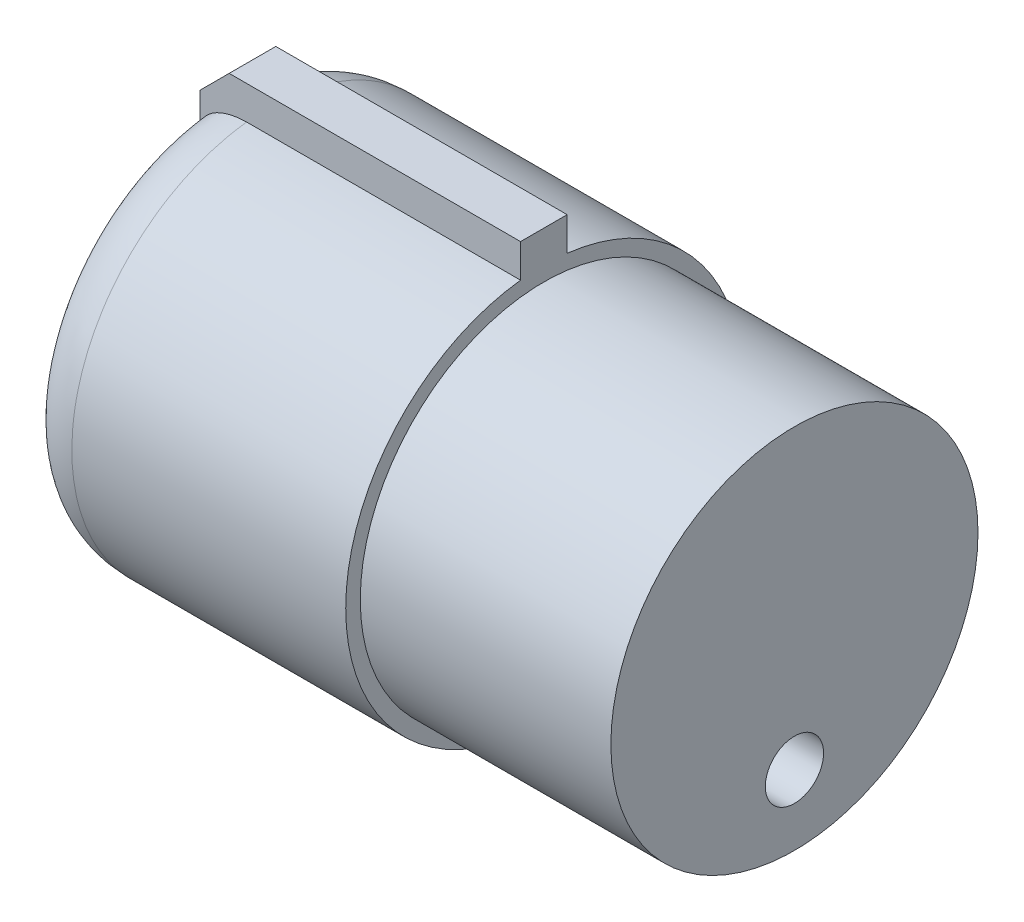
SolidWorks part; units mm, degrees
material "PET"
ref_plane "Front Plane" through (0, 0, 0) normal (0, 0, 1) x (1, 0, 0)
ref_plane "Top Plane" through (0, 0, 0) normal (0, 1, 0) x (1, 0, 0)
ref_plane "Right Plane" through (0, 0, 0) normal (1, 0, 0) x (0, 0, -1)
sketch "Sketch1" plane through (0, 0, 0) normal (0, 0, 1) x (1, 0, 0)
  line L0 (0, 0) -> (8.8, 0) construction
  line L1 (8.8, 0) -> (8.8, 2.5)
  line L2 (8.8, 2.5) -> (4.85, 2.5)
  line L3 (4.85, 2.5) -> (4.85, 2.75)
  line L4 (4.85, 2.75) -> (0, 2.75)
  line L5 (0, 2.75) -> (0, 3.4)
  line L6 (0, 3.4) -> (5.5, 3.4)
  line L7 (5.5, 3.4) -> (5.5, 3.15)
  line L8 (5.5, 3.15) -> (9.8, 3.15)
  line L9 (9.8, 3.15) -> (9.8, 0)
  line L10 (9.8, 0) -> (8.8, 0)
  point P12 (8.8, 0.3857)
  dimension "D1" = 8.8
  dimension "D2" = 1
  dimension "D3" = 3.4
  dimension "D4" = 5.5
  dimension "D5" = 3.15
  dimension "D6" = 0.65
  dimension "D7" = 0.65
  dimension "D8" = 0.65
revolve "Revolve1" add sketch "Sketch1" angle 360 about L0
sketch "Sketch2" plane through (0, 0, 0) normal (-1, 0, 0) x (0, 0, 1)
  line L0 (0, 2.95) -> (0, 0) construction
  line L1 (0.4, 2.95) -> (-0.4, 2.95)
  line L2 (0.4, 2.95) -> (0.4, 3.95)
  line L3 (0.4, 3.95) -> (-0.4, 3.95)
  line L4 (-0.4, 2.95) -> (-0.4, 3.95)
  line L5 (0.4, 2.95) -> (-0.4, 3.95) construction
  line L6 (0.4, 3.95) -> (-0.4, 2.95) construction
  line L7 (0.4, -3.95) -> (-0.4, -3.95)
  line L8 (0.4, -3.95) -> (0.4, -2.95)
  line L9 (0.4, -2.95) -> (-0.4, -2.95)
  line L10 (-0.4, -3.95) -> (-0.4, -2.95)
  line L11 (0.4, -3.95) -> (-0.4, -2.95) construction
  line L12 (0.4, -2.95) -> (-0.4, -3.95) construction
  line L13 (0, 0) -> (0, -2.95) construction
  point P0 (0, 3.45)
  point P5 (0, -3.45)
  point P13 (0, -3.1018)
  dimension "D1" = 7.9
  dimension "D2" = 0.8
  dimension "D3" = 1
extrude "Boss-Extrude1" add sketch "Sketch2" against normal up to surface (5.5 mm away) up to face at (5.5, 0, 3.4)
chamfer "Chamfer1" distance 0.5 angle 45 2 edges at (0, -3.95, 0) (0, 3.95, 0)
fillet "Fillet1" radius 0.8 2 edges at (0, 0, 3.4) (0, 0, -3.4) second distance 0.5 first distance on face at (2.75, 0, 1.9) first distance on face at (2.75, 0, -1.9)
sketch "Sketch3" plane through (9.8, 0, 0) normal (1, 0, 0) x (0, 0, -1)
  line L0 (0, -3.15) -> (0, -1.95) construction
  circle A0 centre (0, 0) radius 3.15 construction
  circle A1 centre (0, 0) radius 3.15 construction
  circle A2 centre (0, -1.95) radius 0.5
  dimension "D2" = 1
  dimension "D1" = 1.2
extrude "Cut-Extrude1" cut sketch "Sketch3" against normal blind 10
